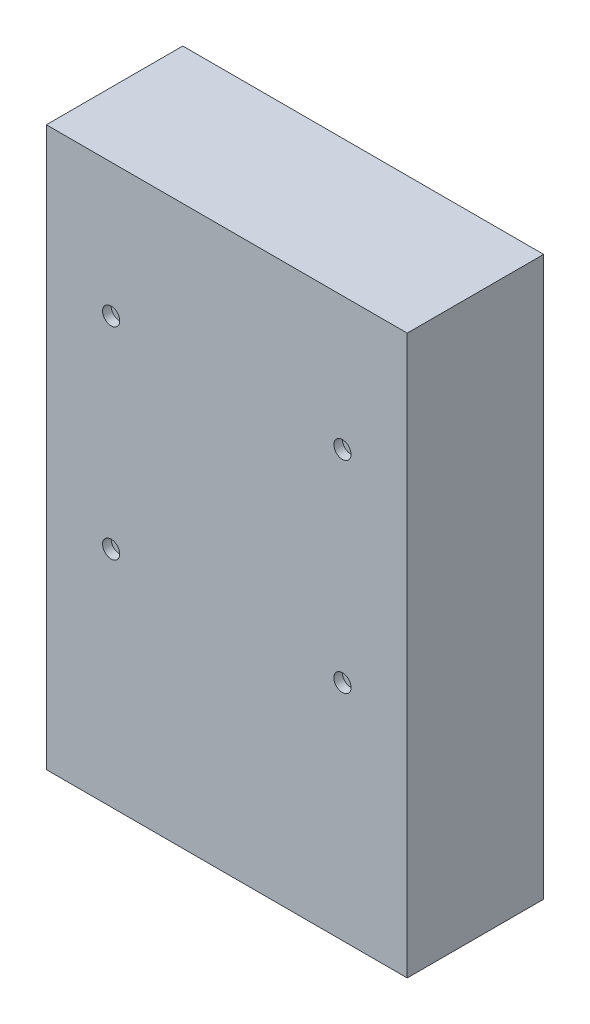
SolidWorks part; units mm, degrees
ref_plane "Front Plane" through (0, 0, 0) normal (0, 0, 1) x (1, 0, 0)
ref_plane "Top Plane" through (0, 0, 0) normal (0, 1, 0) x (1, 0, 0)
ref_plane "Right Plane" through (0, 0, 0) normal (1, 0, 0) x (0, 0, -1)
sketch "Sketch1" plane through (0, 0, 0) normal (0, 0, 1) x (1, 0, 0)
  line L1 (-21, 32.5) -> (21, 32.5)
  line L2 (-21, 32.5) -> (-21, -32.5)
  line L3 (-21, -32.5) -> (21, -32.5)
  line L4 (21, 32.5) -> (21, -32.5)
  line L5 (-21, 32.5) -> (21, -32.5) construction
  line L6 (-21, -32.5) -> (21, 32.5) construction
  point P0 (0, 0)
  dimension "D1" = 65
  dimension "D2" = 42
extrude "Boss-Extrude1" add sketch "Sketch1" along normal blind 15.875
sketch "Sketch2" plane through (0, 0, 15.875) normal (0, 0, 1) x (1, 0, 0)
  line L0 (0, 0) -> (0, -32.5) construction
  line L1 (-21, -32.5) -> (21, -32.5) construction
  circle A0 centre (-13.4595, -6.5) radius 1
  circle A1 centre (-13.4595, 17) radius 1
  circle A4 centre (13.4595, 17) radius 1
  circle A5 centre (13.4595, -6.5) radius 1
  dimension "D2" = 23.5
  dimension "D3" = 2
  dimension "D1" = 26
extrude "Cut-Extrude1" cut sketch "Sketch2" against normal blind 1 and the other way through all
